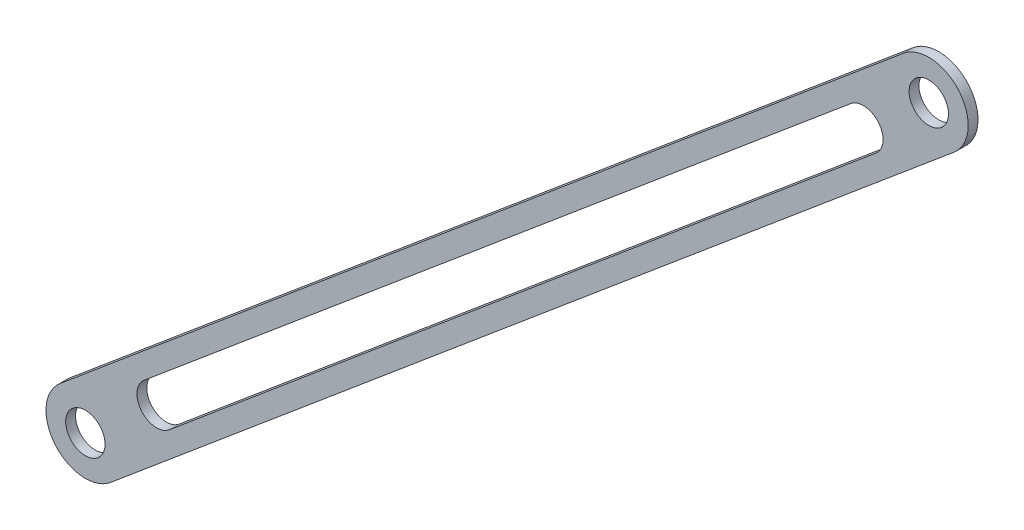
SolidWorks part; units mm, degrees
ref_plane "Front Plane" through (0, 0, 0) normal (0, 0, 1) x (1, 0, 0)
ref_plane "Top Plane" through (0, 0, 0) normal (0, 1, 0) x (1, 0, 0)
ref_plane "Right Plane" through (0, 0, 0) normal (1, 0, 0) x (0, 0, -1)
sketch "Sketch1" plane through (0, 0, 0) normal (0, 0, 1) x (1, 0, 0)
  line L0 (0, 0) -> (179.8502, 0) construction
  line L1 (8.1025, 0) -> (604.1295, 500.126) construction
  line L2 (604.1295, 500.126) -> (692.3152, 0) construction
  line L5 (568.3452, 503.2567) -> (24.3975, 46.8304)
  line L7 (600.9988, 464.3417) -> (57.0511, 7.9154)
  line L9 (542.4916, 448.4057) -> (86.676, 65.931) construction
  line L10 (550.655, 438.6769) -> (94.8394, 56.2022)
  line L11 (534.3282, 458.1345) -> (78.5126, 75.6598)
  line L12 (40.7243, 27.3729) -> (24.3975, 46.8304) construction
  line L13 (40.7243, 27.3729) -> (57.0511, 7.9154) construction
  line L14 (568.3452, 503.2567) -> (600.9988, 464.3417) construction
  arc A0 (550.655, 438.6769) -> (534.3282, 458.1345) centre (542.4916, 448.4057) ccw
  arc A1 (78.5126, 75.6598) -> (94.8394, 56.2022) centre (86.676, 65.931) ccw
  circle A2 centre (40.7243, 27.3729) radius 12.7
  arc A3 (24.3975, 46.8304) -> (57.0511, 7.9154) centre (40.7243, 27.3729) ccw
  circle A4 centre (584.672, 483.7992) radius 12.7
  arc A5 (568.3452, 503.2567) -> (600.9988, 464.3417) centre (584.672, 483.7992) cw
  point P6 (604.1295, 500.126)
  point P12 (314.5838, 257.1683)
  point P24 (584.672, 483.7992)
  point P25 (603.2334, 499.3741)
  dimension "D6" = 25.4
  dimension "D7" = 12.7
  dimension "D4" = 25.4
  dimension "D3" = 25.4
  dimension "D1" = 40
  dimension "D2" = 80
  dimension "D5" = 500.126
extrude "Boss-Extrude1" add sketch "Sketch1" along normal blind 6.35
